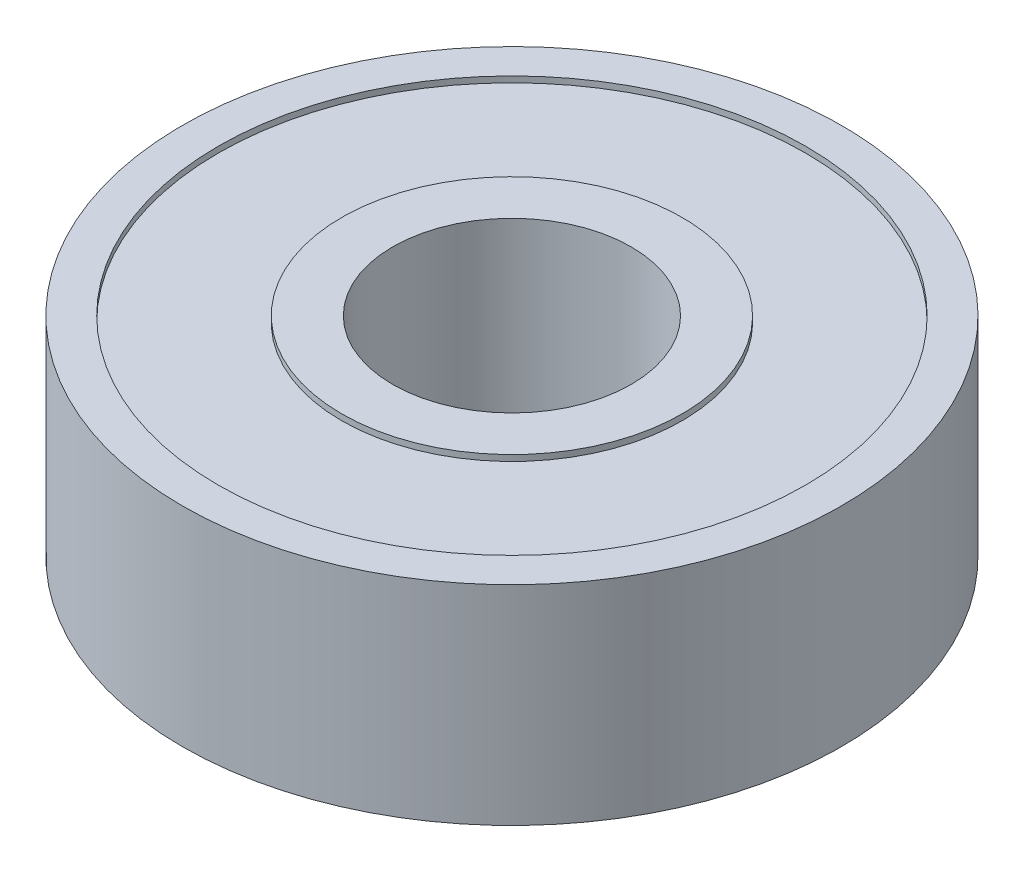
SolidWorks part; units mm, degrees
ref_plane "Front Plane" through (0, 0, 0) normal (0, 0, 1) x (1, 0, 0)
ref_plane "Top Plane" through (0, 0, 0) normal (0, 1, 0) x (1, 0, 0)
ref_plane "Right Plane" through (0, 0, 0) normal (1, 0, 0) x (0, 0, -1)
sketch "Sketch3" plane through (0, 0, 0) normal (0, 1, 0) x (1, 0, 0)
  circle A0 centre (0, 0) radius 3.98
  circle A1 centre (0, 0) radius 11
  dimension "D1" = 7.96
  dimension "D2" = 22
extrude "Boss-Extrude1" add sketch "Sketch3" along normal mid plane 6.96
sketch "Sketch4" plane through (0, 3.48, 0) normal (0, 1, 0) x (1, 0, 0)
  circle A0 centre (0, 0) radius 5.68
  circle A1 centre (0, 0) radius 3.98 construction
  circle A2 centre (0, 0) radius 9.8
  circle A3 centre (0, 0) radius 11 construction
  point P6 (15.8476, -3.895)
  dimension "D1" = 1.7
  dimension "D2" = 1.2
extrude "Cut-Extrude1" cut sketch "Sketch4" against normal blind 0.2
mirror "Mirror1" about plane through (0, 0, 0) normal (0, 1, 0) of "Cut-Extrude1"
